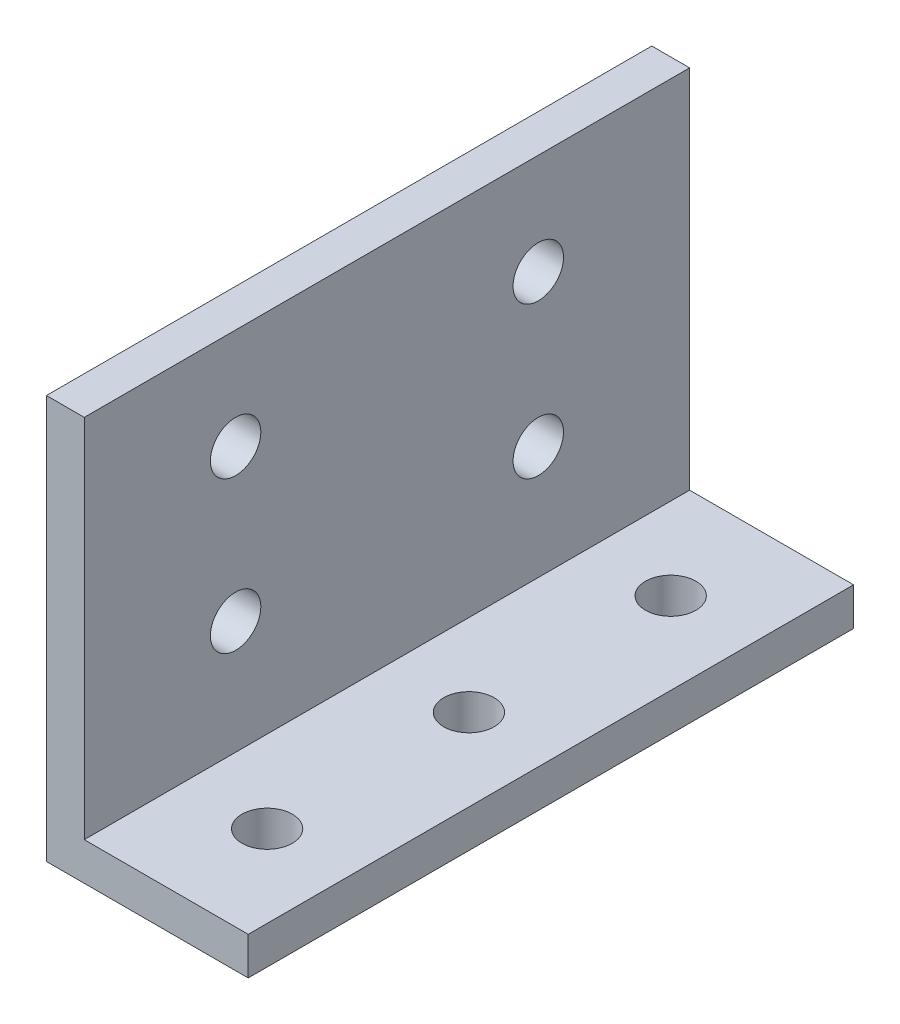
SolidWorks part; units mm, degrees
material "6061 Alloy"
ref_plane "Front Plane" through (0, 0, 0) normal (0, 0, 1) x (1, 0, 0)
ref_plane "Top Plane" through (0, 0, 0) normal (0, 1, 0) x (1, 0, 0)
ref_plane "Right Plane" through (0, 0, 0) normal (1, 0, 0) x (0, 0, -1)
sketch "Sketch1" plane through (0, 0, 0) normal (0, 0, 1) x (1, 0, 0)
  line L0 (0, 0) -> (0, 46.0375)
  line L1 (0, 0) -> (20.6375, 0)
  line L2 (-4.7625, -4.7625) -> (20.6375, -4.7625)
  line L3 (-4.7625, -4.7625) -> (-4.7625, 46.0375)
  line L4 (0, 46.0375) -> (-4.7625, 46.0375)
  line L5 (20.6375, 0) -> (20.6375, -4.7625)
  dimension "D2" = 50.8
  dimension "D3" = 25.4
  dimension "D1" = 4.7625
extrude "Boss-Extrude1" add sketch "Sketch1" along normal blind 76.2
sketch "Sketch2" plane through (0, 0, 0) normal (1, 0, 0) x (0, 0, -1)
  line L0 (-76.2, 46.0375) -> (0, 46.0375) construction
  line L1 (-76.2, 0) -> (-76.2, 46.0375) construction
  circle A0 centre (-57.15, 33.3375) radius 3.175
  circle A1 centre (-19.05, 33.3375) radius 3.175
  circle A3 centre (-19.05, 14.2875) radius 3.175
  circle A5 centre (-57.15, 14.2875) radius 3.175
  dimension "D1" = 6.35
  dimension "D2" = 12.7
  dimension "D3" = 19.05
  dimension "D4" = 2
  dimension "D5" = 2
extrude "Cut-Extrude1" cut sketch "Sketch2" against normal up to next
sketch "Sketch3" plane through (0, 0, 0) normal (0, 1, 0) x (1, 0, 0)
  line L3 (20.6375, -76.2) -> (20.6375, 0) construction
  line L4 (20.6375, -76.2) -> (0, -76.2) construction
  line L5 (10.3187, -63.5) -> (10.3187, -38.1) construction
  point P1 (10.3187, -63.5)
  point P9 (10.3187, -38.1)
  point P11 (10.3187, -12.7)
  dimension "D1" = 10.3187
  dimension "D2" = 12.7
  dimension "D3" = 3
  dimension "D4" = 25.4
hole_wizard "1/4 (0.25) Diameter Hole1" positions "Sketch7" profile "Sketch8" hole size "1/4" standard "ANSI Inch" end condition up to next
sketch "Sketch7" plane through (0, 0, 0) normal (0, 1, 0) x (1, 0, 0)
  point P0 (10.3187, -63.5)
  point P3 (10.3187, -38.1)
  point P6 (10.3187, -12.7)
sketch "Sketch8" plane through (10.3187, 0, 63.5) normal (1, 0, 0) x (0, 0, 1)
  line L0 (0, 0) -> (0, 4.7625)
  line L1 (0, 4.7625) -> (3.175, 4.7625)
  line L2 (3.175, 4.7625) -> (3.175, 0)
  line L5 (3.175, 0) -> (0, 0)
  line L11 (0, -6.35) -> (0, 107.95) construction
  dimension "Thru Hole Dia." = 6.35
  dimension "Thru Hole Depth" = 4.7625
